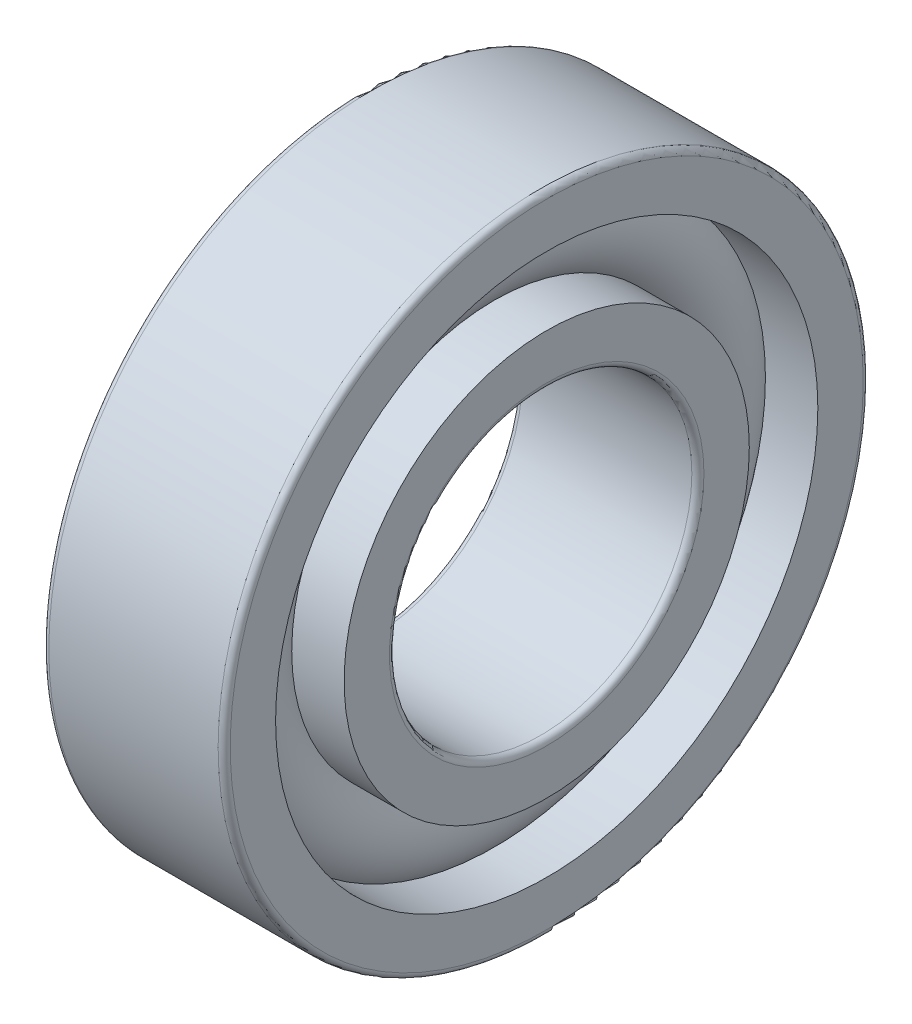
SolidWorks part; units mm, degrees
ref_plane "Plane1" through (0, 0, 0) normal (0, 0, 1) x (1, 0, 0)
ref_plane "Plane2" through (0, 0, 0) normal (0, 1, 0) x (1, 0, 0)
ref_plane "Plane3" through (0, 0, 0) normal (1, 0, 0) x (0, 0, -1)
sketch "Clipboard" plane through (0, 0, 0) normal (0, 0, 1) x (1, 0, 0)
  line L0 (-10, 0) -> (10, 0) construction
  line L1 (0, 0) -> (22.3471, -0.7804)
  line L2 (0, 0) -> (11.7428, 0.4101)
  line L3 (0, 0) -> (22.3471, -0.7804)
  line L4 (0, 0) -> (-22.3573, -0.3902)
  dimension "BallCLRad" = 11.75
sketch "CagSpiSke" plane through (0, 0, 0) normal (0, 0, 1) x (1, 0, 0)
  line L0 (0.255, 11.325) -> (0.255, 12.175)
  line L1 (0.255, 12.175) -> (-0.255, 12.175)
  line L2 (-0.255, 12.175) -> (-0.255, 11.325)
  line L3 (-0.255, 11.325) -> (0.255, 11.325)
  line L4 (-20.6375, 0) -> (20.6375, 0) construction
  line L5 (0, 0) -> (0, 23.7692) construction
  dimension "OD" = 24.35
  dimension "ID" = 22.65
revolve "CageSpine" add sketch "CagSpiSke" angle 0.001 about L4 reverse direction yes
ref_axis "Axis1" through (-50, 0, 0) along (1, 0, 0)
sketch "CagBalSke" plane through (0, 0, 0) normal (0, 0, 1) x (1, 0, 0)
  line L0 (-2.805, 11.75) -> (2.805, 11.75)
  line L1 (-1.905, 11.75) -> (1.905, 11.75) construction
  line L2 (-10, 0) -> (10, 0) construction
  line L3 (0, 0) -> (0, 24) construction
  arc A0 (2.805, 11.75) -> (-2.805, 11.75) centre (0, 11.75) cw
  dimension "BallCLRad" = 11.75
revolve "CageBall" [suppressed] add sketch "CagBalSke" angle 360 about L1 reverse direction yes
pattern_circular "CageBalls" [suppressed] count 2 every 180 about axis through (-50, 0, 0) along (1, 0, 0)
sketch "CagTrmODSke" plane through (0, 0, 0) normal (0, 0, 1) x (1, 0, 0)
  line L0 (2.806, 12.175) -> (2.806, 14.556)
  line L1 (2.806, 14.556) -> (-2.806, 14.556)
  line L2 (-2.806, 14.556) -> (-2.806, 12.175)
  line L3 (-2.806, 12.175) -> (2.806, 12.175)
  line L4 (-20.6375, 0) -> (20.6375, 0) construction
  line L5 (0, 0) -> (0, 25) construction
  dimension "Width" = 5.612
  dimension "ID" = 24.35
  dimension "OD" = 29.112
revolve "CageTrimOD" [suppressed] cut sketch "CagTrmODSke" angle 360 about L4 reverse direction yes
sketch "CagTrmIDSke" plane through (0, 0, 0) normal (0, 0, 1) x (1, 0, 0)
  line L0 (2.806, 8.946) -> (2.806, 11.325)
  line L1 (2.806, 11.325) -> (-2.806, 11.325)
  line L2 (-2.806, 11.325) -> (-2.806, 8.946)
  line L3 (-2.806, 8.946) -> (2.806, 8.946)
  line L4 (-20.6375, 0) -> (20.6375, 0) construction
  line L5 (0, 0) -> (0, 25) construction
  dimension "Width" = 5.612
  dimension "ID" = 17.892
  dimension "OD" = 22.65
revolve "CageTrimID" [suppressed] cut sketch "CagTrmIDSke" angle 360 about L4 reverse direction yes
sketch "BalSimSke" plane through (0, 0, 0) normal (0, 0, 1) x (1, 0, 0)
  line L0 (-10, 0) -> (10, 0) construction
  line L1 (-10, 11.75) -> (10, 11.75) construction
  line L2 (0, 0) -> (0, 23) construction
  circle A0 centre (0, 11.75) radius 2.55
  dimension "BallCLRad" = 11.75
  dimension "Ball_diameter" = 5.1
revolve "BallsSimplified" add sketch "BalSimSke" angle 360 about L0
sketch "BalDetSke" plane through (0, 0, 0) normal (0, 0, 1) x (1, 0, 0)
  line L0 (-2.55, 11.75) -> (2.55, 11.75)
  line L1 (-1.905, 11.75) -> (1.905, 11.75) construction
  line L2 (0, 0) -> (0, 25) construction
  arc A0 (2.55, 11.75) -> (-2.55, 11.75) centre (0, 11.75) cw
  dimension "BallCLRad" = 11.75
  dimension "Ball_diameter" = 5.1
revolve "BallDetailed" [suppressed] add sketch "BalDetSke" angle 360 about L1 reverse direction yes
sketch "InnRacSke" plane through (0, 0, 0) normal (0, 0, 1) x (1, 0, 0)
  line L0 (-1.867, 10.05) -> (-4.5, 10.05)
  line L1 (-4.5, 10.05) -> (-4.5, 7.8)
  line L2 (-4.2, 7.5) -> (4.2, 7.5)
  line L3 (4.5, 7.8) -> (4.5, 10.05)
  line L4 (4.5, 10.05) -> (1.867, 10.05)
  line L5 (-20.6375, 0) -> (20.6375, 0) construction
  line L6 (0, 0) -> (0, 30) construction
  arc A0 (-4.5, 7.8) -> (-4.2, 7.5) centre (-4.2, 7.8) ccw
  arc A1 (4.2, 7.5) -> (4.5, 7.8) centre (4.2, 7.8) ccw
  arc A2 (1.867, 10.05) -> (-1.867, 10.05) centre (0, 11.75) cw
  dimension "BallCLRad" = 11.75
  dimension "Fillet_radius" = 0.3
  dimension "Ball_diameter" = 5.05
  dimension "ID" = 15
  dimension "OD" = 20.1
  dimension "Width" = 9
revolve "InnerRace" add sketch "InnRacSke" angle 360 about L5 reverse direction yes
sketch "OutRacSke" plane through (0, 0, 0) normal (0, 0, 1) x (1, 0, 0)
  line L0 (-1.867, 13.45) -> (-4.5, 13.45)
  line L1 (-4.5, 13.45) -> (-4.5, 15.7)
  line L2 (-4.2, 16) -> (4.2, 16)
  line L3 (4.5, 15.7) -> (4.5, 13.45)
  line L4 (4.5, 13.45) -> (1.867, 13.45)
  line L5 (-20.6375, 0) -> (20.6375, 0) construction
  line L6 (0, 0) -> (0, 30) construction
  arc A0 (-4.5, 15.7) -> (-4.2, 16) centre (-4.2, 15.7) cw
  arc A1 (4.2, 16) -> (4.5, 15.7) centre (4.2, 15.7) cw
  arc A2 (1.867, 13.45) -> (-1.867, 13.45) centre (0, 11.75) ccw
  dimension "BallCLRad" = 11.75
  dimension "Fillet_radius" = 0.3
  dimension "Ball_diameter" = 5.05
  dimension "Width" = 9
revolve "OuterRace" add sketch "OutRacSke" angle 360 about L5 reverse direction yes
pattern_circular "BallsDetailed" [suppressed] count 2 every 180 about axis through (-50, 0, 0) along (1, 0, 0)
equation "\"BallCLRad@Clipboard\" = ( \"OD@OutRacSke\" + \"ID@InnRacSke\" ) / 4"
equation "\"BallCLRad@BalSimSke\" = \"BallCLRad@Clipboard\""
equation "\"BallCLRad@BalDetSke\" = \"BallCLRad@Clipboard\""
equation "\"BallCLRad@InnRacSke\" = \"BallCLRad@Clipboard\""
equation "\"BallCLRad@OutRacSke\" = \"BallCLRad@Clipboard\""
equation "\"Ball_diameter@InnRacSke\" = \"Ball_diameter@BalDetSke\" - 0.05"
equation "\"Ball_diameter@OutRacSke\" = \"Ball_diameter@BalDetSke\" - 0.05"
equation "\"Ball_diameter@BalSimSke\" = \"Ball_diameter@BalDetSke\""
equation "\"Width@OutRacSke\" = \"Width@InnRacSke\""
equation "\"Fillet_radius@OutRacSke\" = \"Fillet_radius@InnRacSke\""
equation "\"Max_count@Clipboard\" = int( 3.14159265 / atn(( \"Ball_diameter@BalDetSke\" / 2) / sqr( \"BallCLRad@Clipboard\"  *  \"BallCLRad@Clipboard\" - ( \"Ball_diameter@BalDetSke\" / 2) *  ( \"Ball_diameter@BalDetSke\" / 2))))"
equation "\"Max_count@Clipboard\" = ((sgn( \"Max_count@Clipboard\" - \"Count@Clipboard\" )-1)*( \"Max_count@Clipboard\" - \"Count@Clipboard\" ))/-2+ \"Count@Clipboard\""
equation "\"Count@BallsDetailed\" = int( \"Show_count@Clipboard\" ) "
equation "\"Count@BallsDetailed\" = ((sgn( \"Count@BallsDetailed\" - \"Max_count@Clipboard\" )-1)*( \"Count@BallsDetailed\" - \"Max_count@Clipboard\" ))/-2+ \"Max_count@Clipboard\""
equation "\"Count@BallsDetailed\" = ((sgn( \"Count@BallsDetailed\" - \"Min_count@Clipboard\" )+1)*( \"Count@BallsDetailed\" - \"Min_count@Clipboard\"))/2 +\"Min_count@Clipboard\""
equation "\"Angle@BallsDetailed\" = 360.0 / \"Max_count@Clipboard\""
equation "\"BallCLRad@CagBalSke\" = \"BallCLRad@Clipboard\""
equation "\"Count@CageBalls\" = \"Count@BallsDetailed\""
equation "\"Angle@CageBalls\" = \"Angle@BallsDetailed\""
equation "\"Angle@CageSpine\" =  \"Angle@CageBalls\" * ( \"Count@CageBalls\" -1 + int( \"Count@CageBalls\" / \"Max_count@Clipboard\" ) )  + 0.001 -  int( \"Count@CageBalls\" / \"Max_count@Clipboard\" ) * 0.001"
equation "\"Angle@CageSpine\" =  \"Angle@CageSpine\" * int( \"Min_count@Clipboard\" / 2) + int(1 / \"Min_count@Clipboard\")  * 0.001"
equation "\"CageWallOD@CagBalSke\" =  \"Ball_diameter@BalDetSke\" * 1.1"
equation "\"Thickness@CagSpiSke\" =  \"Ball_diameter@BalDetSke\" * 0.1"
equation "\"OD@CagTrmODSke\" = \"BallCLRad@Clipboard\" * 2 + \"CageWallOD@CagBalSke\" + 0.002"
equation "\"ID@CagTrmODSke\" = \"BallCLRad@Clipboard\" * 2 + \"Ball_diameter@BalDetSke\" / 6"
equation "\"OD@CagTrmIDSke\" = \"BallCLRad@Clipboard\" * 2 - \"Ball_diameter@BalDetSke\" / 6"
equation "\"ID@CagTrmIDSke\" = \"BallCLRad@Clipboard\" * 2 - \"CageWallOD@CagBalSke\" + 0.002"
equation "\"OD@CagSpiSke\" = \"ID@CagTrmODSke\""
equation "\"ID@CagSpiSke\" = \"OD@CagTrmIDSke\""
equation "\"Width@CagTrmODSke\" = \"CageWallOD@CagBalSke\" + 0.002"
equation "\"Width@CagTrmIDSke\" = \"CageWallOD@CagBalSke\" + 0.002"
